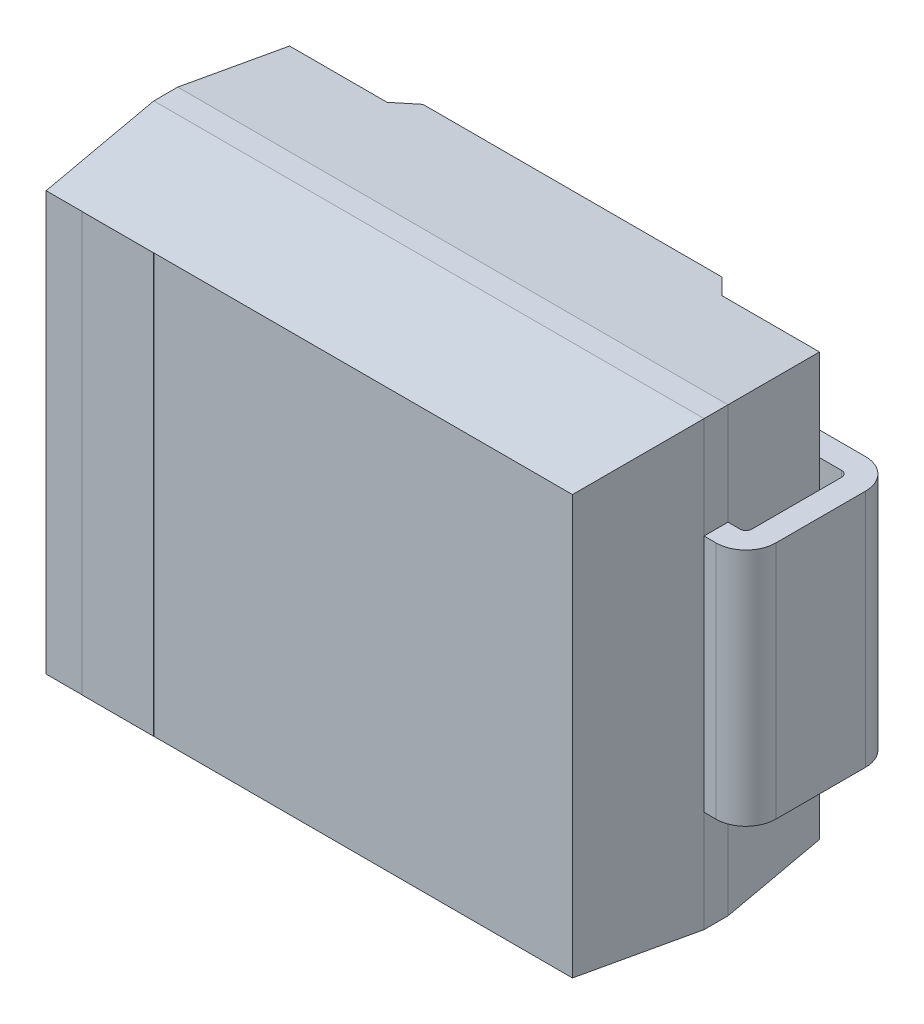
SolidWorks part; units mm, degrees
ref_plane "Płaszczyzna przednia" through (0, 0, 0) normal (0, 0, 1) x (1, 0, 0)
ref_plane "Płaszczyzna górna" through (0, 0, 0) normal (0, 1, 0) x (1, 0, 0)
ref_plane "Płaszczyzna prawa" through (0, 0, 0) normal (1, 0, 0) x (0, 0, -1)
sketch "Szkic1" plane through (0, 0, 0) normal (0, 0, 1) x (1, 0, 0)
  line L1 (2.3, -1.85) -> (-2.3, -1.85)
  line L2 (2.3, -1.85) -> (2.3, 1.85)
  line L3 (2.3, 1.85) -> (-2.3, 1.85)
  line L4 (-2.3, -1.85) -> (-2.3, 1.85)
  line L5 (2.3, -1.85) -> (-2.3, 1.85) construction
  line L6 (2.3, 1.85) -> (-2.3, -1.85) construction
  point P0 (0, 0)
  dimension "D1" = 4.6
  dimension "D2" = 3.7
extrude "Dodanie-wyciągnięcie1" add sketch "Szkic1" along normal blind 2.2
chamfer "Sfazowanie1" distance 1 distance2 0.1 4 edges at (-2.3, 0, 2.2) (0, 1.85, 2.2) (2.3, 0, 2.2) (0, -1.85, 2.2) first distance on face at (-2.3, 0, 1.1) first distance on face at (0, 1.85, 1.1) first distance on face at (2.3, 0, 1.1) first distance on face at (0, -1.85, 1.1)
chamfer "Sfazowanie2" distance 0.1 distance2 1 4 edges at (0, 1.85, 0) (2.3, 0, 0) (0, -1.85, 0) (-2.3, 0, 0) first distance on face at (0, 0, 0)
sketch "Szkic2" plane through (0, 0, 2.2) normal (0, 0, 1) x (1, 0, 0)
  line L0 (-1.9, 1.75) -> (-1.9, -1.75)
  line L5 (-1.9, -1.75) -> (-1.3, -1.75)
  line L6 (-1.3, -1.75) -> (-1.3, 1.75)
  line L7 (-1.3, 1.75) -> (-1.9, 1.75)
  line L8 (-2.2, 1.75) -> (-2.2, -1.75) construction
  line L10 (2.2, 1.75) -> (-2.2, 1.75) construction
  dimension "D1" = 0.3
  dimension "D2" = 0.6
  dimension "D3" = 3.5
extrude "Dodanie-wyciągnięcie2" add sketch "Szkic2" along normal blind 0.001
sketch "Szkic5" plane through (-2.3, 0, 0) normal (-1, 0, 0) x (0, 0, 1)
  line L0 (1, 1.85) -> (1, -1.85) construction
  line L1 (0.15, 1.85) -> (0, 1.85)
  line L2 (0.15, 1.85) -> (0.15, -1.85)
  line L3 (0.15, -1.85) -> (0, -1.85)
  line L4 (0, 1.85) -> (0, -1.85)
  line L5 (1.2, 1.85) -> (1, 1.85) construction
  line L6 (1.2, -1.85) -> (1, -1.85) construction
  dimension "D1" = 1
  dimension "D2" = 0.15
extrude "Wytnij-wyciągnięcie1" cut sketch "Szkic5" against normal blind 0.9
chamfer "Sfazowanie3" distance 0.15 angle 45 1 edges at (-1.4, 0, 0)
sketch "Szkic3" plane through (-2.3, 0, 0) normal (-1, 0, 0) x (0, 0, 1)
  line L0 (1.2, -1.85) -> (1.2, 1.85) construction
  line L1 (1.2, 1) -> (1, 1)
  line L2 (1.2, 1) -> (1.2, -1)
  line L3 (1.2, -1) -> (1, -1)
  line L4 (1, 1) -> (1, -1)
  line L5 (1, 1.85) -> (1, -1.85) construction
  line L6 (1.2, 1.85) -> (1, 1.85) construction
  line L8 (1.2, 0) -> (1, 0) construction
  dimension "D1" = 0.85
  dimension "D2" = 2
  dimension "D3" = 0.2
sketch "Szkic4" plane through (0, 0, 0) normal (0, 1, 0) x (1, 0, 0)
  line L0 (-2.3, -1.2) -> (-2.4, -1.2)
  line L1 (-2.65, -0.95) -> (-2.65, -0.2)
  line L2 (-2.4, 0.05) -> (-1.55, 0.05)
  arc A0 (-2.65, -0.2) -> (-2.4, 0.05) centre (-2.4, -0.2) cw
  arc A1 (-2.4, -1.2) -> (-2.65, -0.95) centre (-2.4, -0.95) cw
  point P7 (-2.65, 0.05)
  point P10 (-2.65, -1.2)
  dimension "D4" = 0.25
  dimension "D1" = 0.35
  dimension "D2" = 1.25
  dimension "D3" = 1.1
sweep "Wyciągnięcie po ścieżce1" add profiles "Szkic3" path "Szkic4"
mirror "Lustro1" about plane through (0, 0, 0) normal (1, 0, 0) of "Wyciągnięcie po ścieżce1", "Sfazowanie3", "Wytnij-wyciągnięcie1"
